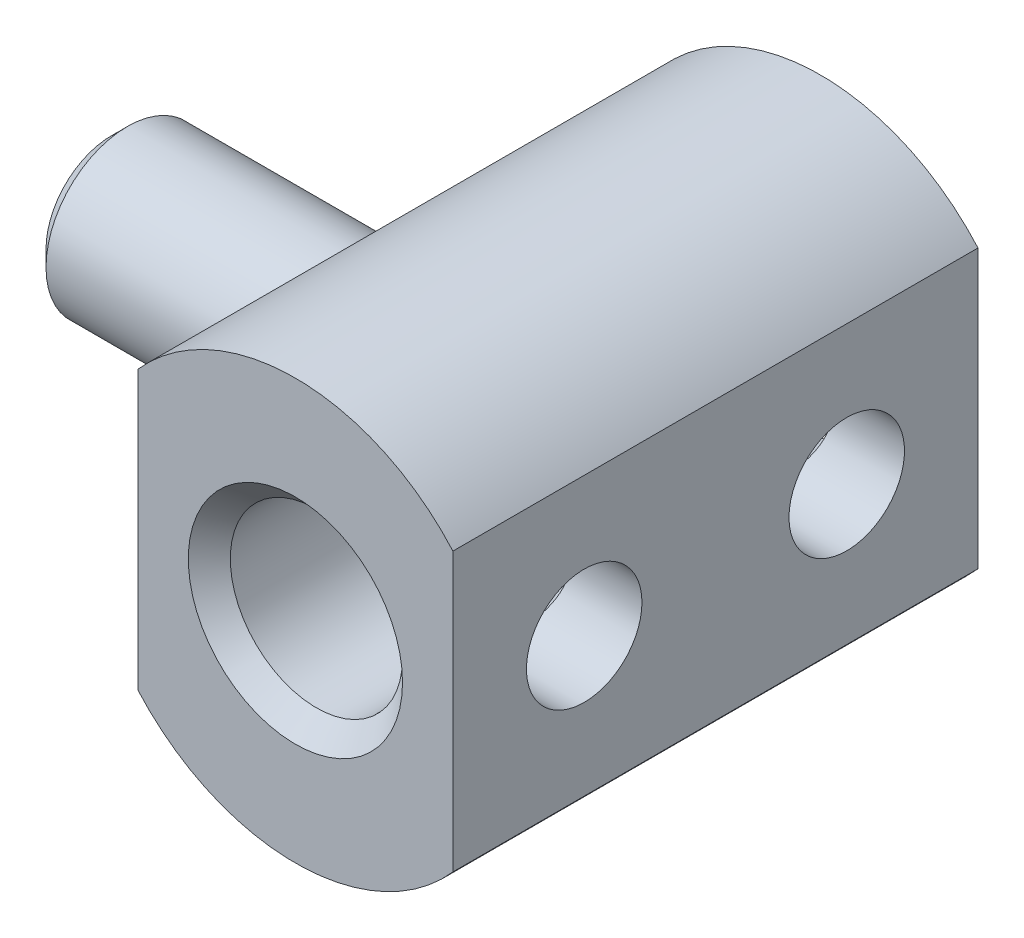
SolidWorks part; units mm, degrees
material "PLA2"
ref_plane "Front Plane" through (0, 0, 0) normal (0, 0, 1) x (1, 0, 0)
ref_plane "Top Plane" through (0, 0, 0) normal (0, 1, 0) x (1, 0, 0)
ref_plane "Right Plane" through (0, 0, 0) normal (1, 0, 0) x (0, 0, -1)
sketch "Sketch1" plane through (0, 0, 0) normal (0, 0, 1) x (1, 0, 0)
  circle A0 centre (0, 0) radius 2.0828
  circle A1 centre (0, 0) radius 5.08
  dimension "D1" = 4.1656
  dimension "D2" = 10.16
extrude "Boss-Extrude1" add sketch "Sketch1" along normal mid plane 12.7
sketch "Sketch3" plane through (0, 0, 6.35) normal (0, 0, 1) x (1, 0, 0)
  line L0 (-3.81, 3.3601) -> (-3.81, -3.3601)
  line L1 (0, 0.0885) -> (0, 50000.0885) construction
  line L2 (3.81, 3.3601) -> (3.81, -3.3601)
  arc A0 (-3.81, 3.3601) -> (-3.81, -3.3601) centre (0, 0) ccw
  arc A1 (3.81, 3.3601) -> (3.81, -3.3601) centre (0, 0) cw
  circle A3 centre (0, 0) radius 5.08 construction
  point P1 (-5.08, 0)
  dimension "D1" = 1.27
extrude "Cut-Extrude1" cut sketch "Sketch3" against normal through all
sketch "Sketch4" plane through (-3.81, 0, 0) normal (-1, 0, 0) x (0, 0, 1)
  circle A0 centre (0, 0) radius 1.9685
  dimension "D1" = 3.937
extrude "Boss-Extrude2" add sketch "Sketch4" along normal blind 6.985
fillet "Fillet1" radius 1.27 1 edges at (-3.81, 0, 1.9685)
chamfer "Chamfer1" distance 0.381 angle 45 1 edges at (-10.795, 0, 1.9685)
sketch "Sketch5" plane through (3.81, 0, 0) normal (1, 0, 0) x (0, 0, -1)
  line L0 (0, 0) -> (0, 50000) construction
  line L1 (-3.175, 0) -> (0, 0) construction
  circle A0 centre (-3.175, 0) radius 1.397
  circle A1 centre (3.175, 0) radius 1.397
  dimension "D1" = 2.794
  dimension "D2" = 6.35
extrude "Cut-Extrude2" cut sketch "Sketch5" against normal blind 3.81
chamfer "Chamfer2" distance 0.508 angle 45 2 edges at (2.0828, 0, -6.35) (2.0828, 0, 6.35)
